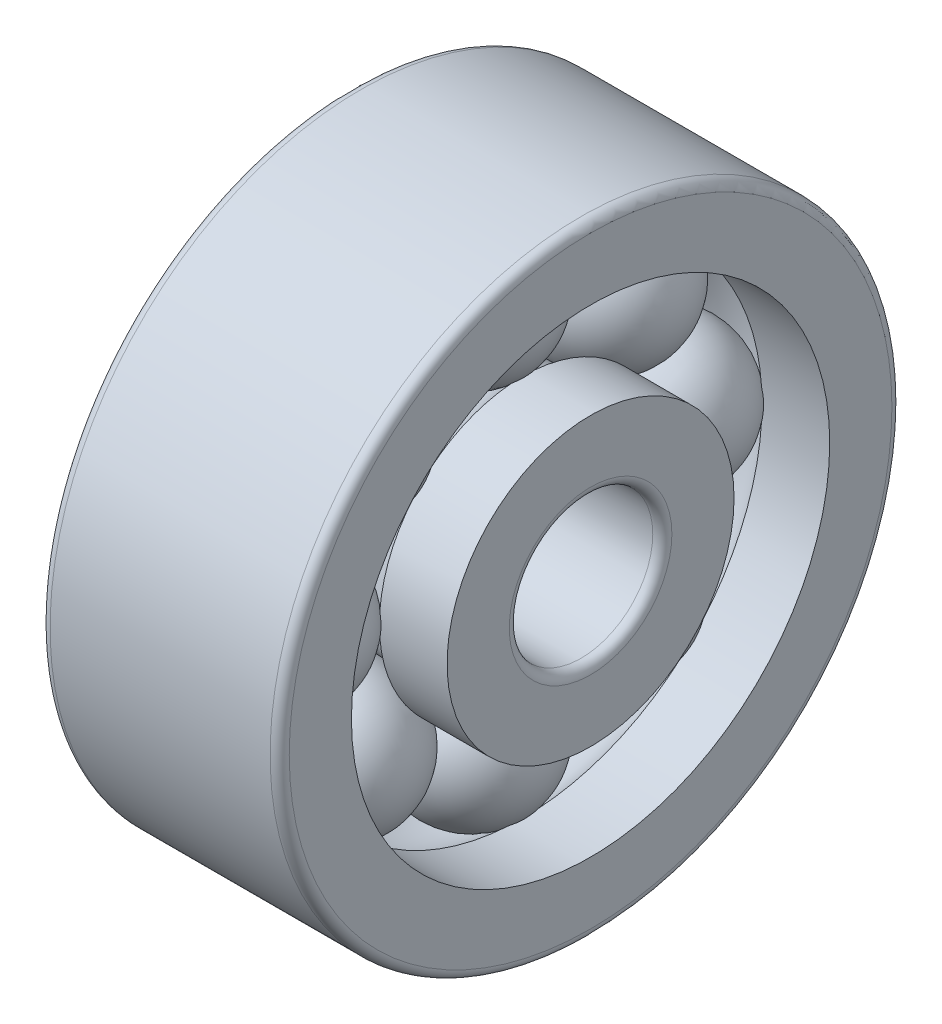
SolidWorks part; units mm, degrees
ref_plane "Plane1" through (0, 0, 0) normal (0, 0, 1) x (1, 0, 0)
ref_plane "Plane2" through (0, 0, 0) normal (0, 1, 0) x (1, 0, 0)
ref_plane "Plane3" through (0, 0, 0) normal (1, 0, 0) x (0, 0, -1)
sketch "Clipboard" plane through (0, 0, 0) normal (0, 0, 1) x (1, 0, 0)
  line L0 (-10, 0) -> (10, 0) construction
  line L1 (0, 0) -> (22.1431, -3.112)
  line L2 (0, 0) -> (3.9994, -0.0698)
  line L3 (0, 0) -> (22.3573, 0.3902)
  line L4 (0, 0) -> (-22.3573, -0.3902)
  dimension "BallCLRad" = 4
sketch "CagSpiSke" plane through (0, 0, 0) normal (0, 0, 1) x (1, 0, 0)
  line L0 (0.15, 3.75) -> (0.15, 4.25)
  line L1 (0.15, 4.25) -> (-0.15, 4.25)
  line L2 (-0.15, 4.25) -> (-0.15, 3.75)
  line L3 (-0.15, 3.75) -> (0.15, 3.75)
  line L4 (-20.6375, 0) -> (20.6375, 0) construction
  line L5 (0, 0) -> (0, 23.7692) construction
  dimension "OD" = 8.5
  dimension "ID" = 7.5
revolve "CageSpine" add sketch "CagSpiSke" angle 0.001 about L4 reverse direction yes
ref_axis "Axis1" through (-50, 0, 0) along (1, 0, 0)
sketch "CagBalSke" plane through (0, 0, 0) normal (0, 0, 1) x (1, 0, 0)
  line L0 (-1.65, 4) -> (1.65, 4)
  line L1 (-1.905, 4) -> (1.905, 4) construction
  line L2 (-10, 0) -> (10, 0) construction
  line L3 (0, 0) -> (0, 24) construction
  arc A0 (1.65, 4) -> (-1.65, 4) centre (0, 4) cw
  dimension "BallCLRad" = 4
revolve "CageBall" [suppressed] add sketch "CagBalSke" angle 360 about L1 reverse direction yes
pattern_circular "CageBalls" [suppressed] count 8 every 45 about axis through (-50, 0, 0) along (1, 0, 0)
sketch "CagTrmODSke" plane through (0, 0, 0) normal (0, 0, 1) x (1, 0, 0)
  line L0 (1.651, 4.25) -> (1.651, 5.651)
  line L1 (1.651, 5.651) -> (-1.651, 5.651)
  line L2 (-1.651, 5.651) -> (-1.651, 4.25)
  line L3 (-1.651, 4.25) -> (1.651, 4.25)
  line L4 (-20.6375, 0) -> (20.6375, 0) construction
  line L5 (0, 0) -> (0, 25) construction
  dimension "Width" = 3.302
  dimension "ID" = 8.5
  dimension "OD" = 11.302
revolve "CageTrimOD" [suppressed] cut sketch "CagTrmODSke" angle 360 about L4 reverse direction yes
sketch "CagTrmIDSke" plane through (0, 0, 0) normal (0, 0, 1) x (1, 0, 0)
  line L0 (1.651, 2.351) -> (1.651, 3.75)
  line L1 (1.651, 3.75) -> (-1.651, 3.75)
  line L2 (-1.651, 3.75) -> (-1.651, 2.351)
  line L3 (-1.651, 2.351) -> (1.651, 2.351)
  line L4 (-20.6375, 0) -> (20.6375, 0) construction
  line L5 (0, 0) -> (0, 25) construction
  dimension "Width" = 3.302
  dimension "ID" = 4.702
  dimension "OD" = 7.5
revolve "CageTrimID" [suppressed] cut sketch "CagTrmIDSke" angle 360 about L4 reverse direction yes
sketch "BalSimSke" plane through (0, 0, 0) normal (0, 0, 1) x (1, 0, 0)
  line L0 (-10, 0) -> (10, 0) construction
  line L1 (-10, 4) -> (10, 4) construction
  line L2 (0, 0) -> (0, 23) construction
  circle A0 centre (0, 4) radius 1.5
  dimension "BallCLRad" = 4
  dimension "Ball_diameter" = 3
revolve "BallsSimplified" [suppressed] add sketch "BalSimSke" angle 360 about L0
sketch "BalDetSke" plane through (0, 0, 0) normal (0, 0, 1) x (1, 0, 0)
  line L0 (-1.5, 4) -> (1.5, 4)
  line L1 (-1.905, 4) -> (1.905, 4) construction
  line L2 (0, 0) -> (0, 25) construction
  arc A0 (1.5, 4) -> (-1.5, 4) centre (0, 4) cw
  dimension "BallCLRad" = 4
  dimension "Ball_diameter" = 3
revolve "BallDetailed" add sketch "BalDetSke" angle 360 about L1 reverse direction yes
sketch "InnRacSke" plane through (0, 0, 0) normal (0, 0, 1) x (1, 0, 0)
  line L0 (-1.0843, 3) -> (-2.5, 3)
  line L1 (-2.5, 3) -> (-2.5, 1.7)
  line L2 (-2.3, 1.5) -> (2.3, 1.5)
  line L3 (2.5, 1.7) -> (2.5, 3)
  line L4 (2.5, 3) -> (1.0843, 3)
  line L5 (-20.6375, 0) -> (20.6375, 0) construction
  line L6 (0, 0) -> (0, 30) construction
  arc A0 (-2.5, 1.7) -> (-2.3, 1.5) centre (-2.3, 1.7) ccw
  arc A1 (2.3, 1.5) -> (2.5, 1.7) centre (2.3, 1.7) ccw
  arc A2 (1.0843, 3) -> (-1.0843, 3) centre (0, 4) cw
  dimension "BallCLRad" = 4
  dimension "Fillet_radius" = 0.2
  dimension "Ball_diameter" = 2.95
  dimension "ID" = 3
  dimension "OD" = 6
  dimension "Width" = 5
revolve "InnerRace" add sketch "InnRacSke" angle 360 about L5 reverse direction yes
sketch "OutRacSke" plane through (0, 0, 0) normal (0, 0, 1) x (1, 0, 0)
  line L0 (-1.0843, 5) -> (-2.5, 5)
  line L1 (-2.5, 5) -> (-2.5, 6.3)
  line L2 (-2.3, 6.5) -> (2.3, 6.5)
  line L3 (2.5, 6.3) -> (2.5, 5)
  line L4 (2.5, 5) -> (1.0843, 5)
  line L5 (-20.6375, 0) -> (20.6375, 0) construction
  line L6 (0, 0) -> (0, 30) construction
  arc A0 (-2.5, 6.3) -> (-2.3, 6.5) centre (-2.3, 6.3) cw
  arc A1 (2.3, 6.5) -> (2.5, 6.3) centre (2.3, 6.3) cw
  arc A2 (1.0843, 5) -> (-1.0843, 5) centre (0, 4) ccw
  dimension "BallCLRad" = 4
  dimension "Fillet_radius" = 0.2
  dimension "Ball_diameter" = 2.95
  dimension "Width" = 5
revolve "OuterRace" add sketch "OutRacSke" angle 360 about L5 reverse direction yes
pattern_circular "BallsDetailed" count 8 every 45 about axis through (-50, 0, 0) along (1, 0, 0) of "BallDetailed"
equation "\"BallCLRad@Clipboard\" = ( \"OD@OutRacSke\" + \"ID@InnRacSke\" ) / 4"
equation "\"BallCLRad@BalSimSke\" = \"BallCLRad@Clipboard\""
equation "\"BallCLRad@BalDetSke\" = \"BallCLRad@Clipboard\""
equation "\"BallCLRad@InnRacSke\" = \"BallCLRad@Clipboard\""
equation "\"BallCLRad@OutRacSke\" = \"BallCLRad@Clipboard\""
equation "\"Ball_diameter@InnRacSke\" = \"Ball_diameter@BalDetSke\" - 0.05"
equation "\"Ball_diameter@OutRacSke\" = \"Ball_diameter@BalDetSke\" - 0.05"
equation "\"Ball_diameter@BalSimSke\" = \"Ball_diameter@BalDetSke\""
equation "\"Width@OutRacSke\" = \"Width@InnRacSke\""
equation "\"Fillet_radius@OutRacSke\" = \"Fillet_radius@InnRacSke\""
equation "\"Max_count@Clipboard\" = int( 3.14159265 / atn(( \"Ball_diameter@BalDetSke\" / 2) / sqr( \"BallCLRad@Clipboard\"  *  \"BallCLRad@Clipboard\" - ( \"Ball_diameter@BalDetSke\" / 2) *  ( \"Ball_diameter@BalDetSke\" / 2))))"
equation "\"Max_count@Clipboard\" = ((sgn( \"Max_count@Clipboard\" - \"Count@Clipboard\" )-1)*( \"Max_count@Clipboard\" - \"Count@Clipboard\" ))/-2+ \"Count@Clipboard\""
equation "\"Count@BallsDetailed\" = int( \"Show_count@Clipboard\" ) "
equation "\"Count@BallsDetailed\" = ((sgn( \"Count@BallsDetailed\" - \"Max_count@Clipboard\" )-1)*( \"Count@BallsDetailed\" - \"Max_count@Clipboard\" ))/-2+ \"Max_count@Clipboard\""
equation "\"Count@BallsDetailed\" = ((sgn( \"Count@BallsDetailed\" - \"Min_count@Clipboard\" )+1)*( \"Count@BallsDetailed\" - \"Min_count@Clipboard\"))/2 +\"Min_count@Clipboard\""
equation "\"Angle@BallsDetailed\" = 360.0 / \"Max_count@Clipboard\""
equation "\"BallCLRad@CagBalSke\" = \"BallCLRad@Clipboard\""
equation "\"Count@CageBalls\" = \"Count@BallsDetailed\""
equation "\"Angle@CageBalls\" = \"Angle@BallsDetailed\""
equation "\"Angle@CageSpine\" =  \"Angle@CageBalls\" * ( \"Count@CageBalls\" -1 + int( \"Count@CageBalls\" / \"Max_count@Clipboard\" ) )  + 0.001 -  int( \"Count@CageBalls\" / \"Max_count@Clipboard\" ) * 0.001"
equation "\"Angle@CageSpine\" =  \"Angle@CageSpine\" * int( \"Min_count@Clipboard\" / 2) + int(1 / \"Min_count@Clipboard\")  * 0.001"
equation "\"CageWallOD@CagBalSke\" =  \"Ball_diameter@BalDetSke\" * 1.1"
equation "\"Thickness@CagSpiSke\" =  \"Ball_diameter@BalDetSke\" * 0.1"
equation "\"OD@CagTrmODSke\" = \"BallCLRad@Clipboard\" * 2 + \"CageWallOD@CagBalSke\" + 0.002"
equation "\"ID@CagTrmODSke\" = \"BallCLRad@Clipboard\" * 2 + \"Ball_diameter@BalDetSke\" / 6"
equation "\"OD@CagTrmIDSke\" = \"BallCLRad@Clipboard\" * 2 - \"Ball_diameter@BalDetSke\" / 6"
equation "\"ID@CagTrmIDSke\" = \"BallCLRad@Clipboard\" * 2 - \"CageWallOD@CagBalSke\" + 0.002"
equation "\"OD@CagSpiSke\" = \"ID@CagTrmODSke\""
equation "\"ID@CagSpiSke\" = \"OD@CagTrmIDSke\""
equation "\"Width@CagTrmODSke\" = \"CageWallOD@CagBalSke\" + 0.002"
equation "\"Width@CagTrmIDSke\" = \"CageWallOD@CagBalSke\" + 0.002"
